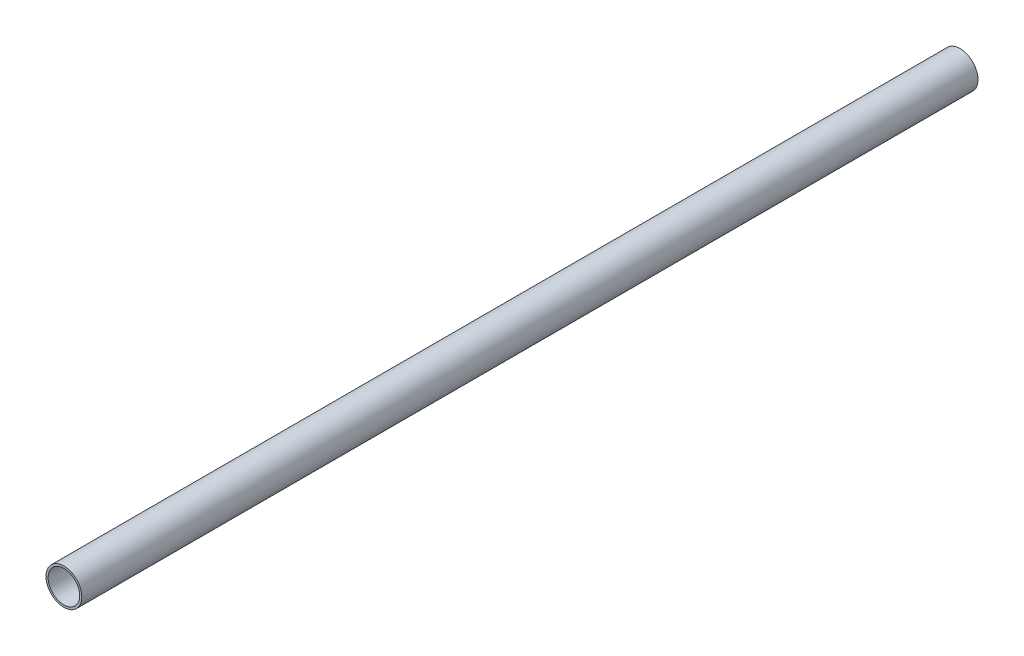
SolidWorks part; units mm, degrees
material "PE Высокой плотности"
ref_plane "Front" through (0, 0, 0) normal (0, 0, 1) x (1, 0, 0)
ref_plane "Top" through (0, 0, 0) normal (0, 1, 0) x (1, 0, 0)
ref_plane "Side" through (0, 0, 0) normal (1, 0, 0) x (0, 0, -1)
sketch "PipeSketch" plane through (0, 0, 0) normal (0, 0, 1) x (1, 0, 0)
  circle A0 centre (0, 0) radius 16
  circle A1 centre (0, 0) radius 14.1
  dimension "OuterDiameter" = 32
  dimension "InnerDiameter" = 28.2
extrude "Extrusion" add sketch "PipeSketch" along normal blind 800
sketch "FilterSketch" plane through (0, 0, 0) normal (0, 0, 1) x (1, 0, 0)
  circle A0 centre (0, 0) radius 16 construction
  dimension "NominalDiameter" = 32
